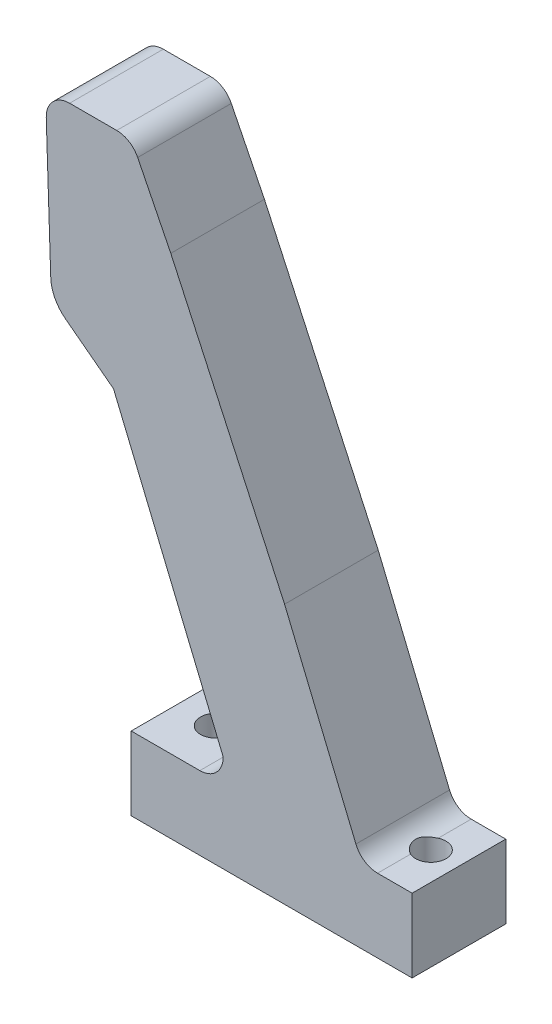
SolidWorks part; units mm, degrees
ref_plane "Front Plane" through (0, 0, 0) normal (0, 0, 1) x (1, 0, 0)
ref_plane "Top Plane" through (0, 0, 0) normal (0, 1, 0) x (1, 0, 0)
ref_plane "Right Plane" through (0, 0, 0) normal (1, 0, 0) x (0, 0, -1)
sketch "Sketch1" plane through (0, 0, 0) normal (0, 0, 1) x (1, 0, 0)
  line L2 (-44.0978, -29.1565) -> (-44.0978, -44.8501)
  line L3 (-44.0978, -44.8501) -> (15.9022, -44.8501)
  line L7 (-35.9155, -29.1565) -> (-44.0978, -29.1565)
  line L10 (-58.1484, 40.0615) -> (-47.8781, 32.2588)
  line L14 (-29.4383, -29.1565) -> (-35.9155, -29.1565)
  line L15 (15.9022, -44.8501) -> (15.9022, -29.1565)
  line L16 (15.9022, -29.1565) -> (8.5166, -29.1565)
  line L18 (-47.8781, 32.2588) -> (-24.4383, -24.1565)
  line L19 (15.8445, -44.8501) -> (15.9599, -44.8501) construction
  line L20 (3.898, -26.0718) -> (-11.3405, 10.674)
  line L21 (-11.3405, 10.674) -> (-35.6415, 63.4231)
  line L26 (-61.2932, 46.4002) -> (-62.2447, 75.2171)
  line L27 (-57.2475, 80.3821) -> (-47.1917, 80.3821)
  line L28 (-42.7172, 77.6133) -> (-35.6415, 63.4231)
  arc A7 (-61.2932, 46.4002) -> (-58.1484, 40.0615) centre (-53.3327, 46.4002) ccw
  arc A13 (8.5166, -29.1565) -> (3.898, -26.0718) centre (8.5166, -24.1565) cw
  arc A14 (-24.4383, -24.1565) -> (-29.4383, -29.1565) centre (-29.4383, -24.1565) cw
  arc A17 (-62.2447, 75.2171) -> (-57.2475, 80.3821) centre (-57.2475, 75.3821) cw
  arc A18 (-47.1917, 80.3821) -> (-42.7172, 77.6133) centre (-47.1917, 75.3821) cw
  dimension "D1" = 5
  dimension "D2" = 5
extrude "Boss-Extrude1" add sketch "Sketch1" along normal blind 20
sketch "Sketch3" plane through (0, -29.1565, 0) normal (0, 1, 0) x (1, 0, 0)
  line L0 (15.9022, -20) -> (15.9022, 0) construction
  circle A0 centre (9.9022, -10) radius 3.25
  circle A1 centre (-36.0384, -10) radius 3.25
  dimension "D2" = 6.5
  dimension "D3" = 6.5
  dimension "D1" = 6
extrude "Cut-Extrude1" cut sketch "Sketch3" against normal blind 20 and the other way blind 20
